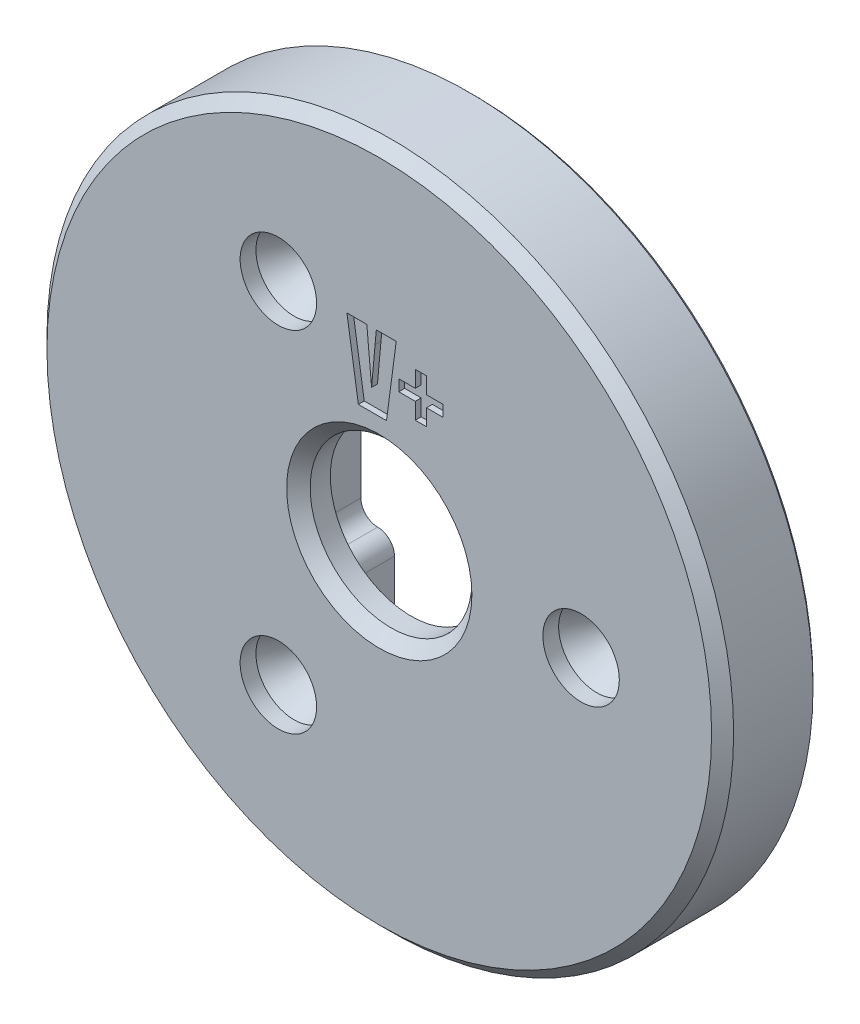
SolidWorks part; units mm, degrees
other "标注1"
sketch "草图9" plane through (123, 77, 0) normal (0.3334, -0.0407, -0.9419) x (-0.9427, 0, -0.3337)
material "有机玻璃 (TM) GS 丙烯酸铸钣"
ref_plane "前视基准面" through (0, 0, 0) normal (0, 0, 1) x (1, 0, 0)
ref_plane "上视基准面" through (0, 0, 0) normal (0, 1, 0) x (1, 0, 0)
ref_plane "右视基准面" through (0, 0, 0) normal (1, 0, 0) x (0, 0, -1)
sketch "草图2" plane through (0, 0, 0) normal (0, 0, 1) x (1, 0, 0)
  circle A2 centre (100, 100) radius 21.8
sketch "草图3" plane through (0, 0, 0) normal (0, 0, 1) x (1, 0, 0)
  circle A0 centre (100, 100) radius 23.35
extrude "凸台-拉伸3" add sketch "草图3" along normal blind 6.4
extrude "切除-拉伸1" cut sketch "草图2" along normal blind 1.63
sketch "草图4" plane through (0, 0, 0) normal (0, 0, 1) x (1, 0, 0)
  line L0 (83.312, 98.171) -> (83.312, 101.854)
  line L1 (83.566, 97.917) -> (86.868, 97.917)
  line L2 (87.122, 98.171) -> (87.122, 101.727)
  line L3 (83.566, 102.108) -> (86.741, 102.108)
  line L4 (98.171, 114.173) -> (98.171, 115.57)
  line L5 (96.901, 114.173) -> (98.171, 114.173)
  line L6 (96.393, 106.045) -> (96.393, 113.665)
  line L7 (93.98, 97.155) -> (93.98, 103.632)
  line L8 (96.266, 83.693) -> (96.266, 94.869)
  line L9 (96.901, 83.058) -> (102.489, 83.058)
  line L10 (103.759, 84.328) -> (106.807, 84.328)
  line L11 (107.188, 84.709) -> (108.712, 84.709)
  line L12 (109.347, 85.344) -> (109.347, 86.868)
  line L13 (109.855, 87.376) -> (110.871, 87.376)
  line L14 (111.379, 87.884) -> (111.379, 88.646)
  line L15 (111.887, 89.154) -> (114.046, 89.154)
  line L16 (114.554, 89.662) -> (114.554, 91.059)
  line L17 (115.062, 91.567) -> (115.189, 91.567)
  line L18 (115.824, 92.202) -> (115.824, 94.615)
  line L19 (106.299, 94.869) -> (115.57, 94.869)
  line L20 (105.791, 95.377) -> (105.791, 102.616)
  line L21 (106.426, 103.251) -> (115.443, 103.251)
  line L22 (116.586, 102.108) -> (117.983, 102.108)
  line L23 (118.237, 102.362) -> (118.237, 102.997)
  line L24 (116.713, 104.521) -> (116.713, 109.093)
  line L25 (111.252, 109.855) -> (115.951, 109.855)
  line L26 (110.744, 110.363) -> (110.744, 113.411)
  line L27 (103.632, 114.427) -> (109.728, 114.427)
  line L28 (103.251, 114.808) -> (103.251, 115.57)
  line L29 (98.552, 115.951) -> (102.87, 115.951)
  arc A60 (83.566, 102.108) -> (83.312, 101.854) centre (83.566, 101.854) ccw
  arc A63 (83.312, 98.171) -> (83.566, 97.917) centre (83.566, 98.171) ccw
  arc A66 (86.868, 97.917) -> (87.122, 98.171) centre (86.868, 98.171) ccw
  arc A69 (87.122, 101.727) -> (86.741, 102.108) centre (86.741, 101.727) ccw
  arc A72 (98.552, 115.951) -> (98.171, 115.57) centre (98.552, 115.57) ccw
  arc A75 (96.901, 114.173) -> (96.393, 113.665) centre (96.901, 113.665) ccw
  arc A78 (95.25, 104.902) -> (96.393, 106.045) centre (95.25, 106.045) ccw
  arc A81 (95.25, 104.902) -> (93.98, 103.632) centre (95.25, 103.632) ccw
  arc A84 (93.98, 97.155) -> (95.123, 96.012) centre (95.123, 97.155) ccw
  arc A87 (96.266, 94.869) -> (95.123, 96.012) centre (95.123, 94.869) ccw
  arc A90 (96.266, 83.693) -> (96.901, 83.058) centre (96.901, 83.693) ccw
  arc A93 (102.489, 83.058) -> (102.87, 83.439) centre (102.489, 83.439) ccw
  arc A96 (103.759, 84.328) -> (102.87, 83.439) centre (103.759, 83.439) ccw
  arc A99 (106.807, 84.328) -> (106.934, 84.455) centre (106.807, 84.455) ccw
  arc A102 (107.188, 84.709) -> (106.934, 84.455) centre (107.188, 84.455) ccw
  arc A105 (108.712, 84.709) -> (109.347, 85.344) centre (108.712, 85.344) ccw
  arc A108 (109.855, 87.376) -> (109.347, 86.868) centre (109.855, 86.868) ccw
  arc A111 (110.871, 87.376) -> (111.379, 87.884) centre (110.871, 87.884) ccw
  arc A114 (111.887, 89.154) -> (111.379, 88.646) centre (111.887, 88.646) ccw
  arc A117 (114.046, 89.154) -> (114.554, 89.662) centre (114.046, 89.662) ccw
  arc A120 (115.062, 91.567) -> (114.554, 91.059) centre (115.062, 91.059) ccw
  arc A123 (115.189, 91.567) -> (115.824, 92.202) centre (115.189, 92.202) ccw
  arc A126 (115.824, 94.615) -> (115.57, 94.869) centre (115.57, 94.615) ccw
  arc A129 (105.791, 95.377) -> (106.299, 94.869) centre (106.299, 95.377) ccw
  arc A132 (106.426, 103.251) -> (105.791, 102.616) centre (106.426, 102.616) ccw
  arc A135 (116.078, 102.616) -> (115.443, 103.251) centre (115.443, 102.616) ccw
  arc A138 (116.078, 102.616) -> (116.586, 102.108) centre (116.586, 102.616) ccw
  arc A141 (117.983, 102.108) -> (118.237, 102.362) centre (117.983, 102.362) ccw
  arc A144 (118.237, 102.997) -> (117.729, 103.505) centre (117.729, 102.997) ccw
  arc A147 (116.713, 104.521) -> (117.729, 103.505) centre (117.729, 104.521) ccw
  arc A150 (116.713, 109.093) -> (115.951, 109.855) centre (115.951, 109.093) ccw
  arc A153 (110.744, 110.363) -> (111.252, 109.855) centre (111.252, 110.363) ccw
  arc A156 (110.744, 113.411) -> (109.728, 114.427) centre (109.728, 113.411) ccw
  arc A159 (103.251, 114.808) -> (103.632, 114.427) centre (103.632, 114.808) ccw
  arc A162 (103.251, 115.57) -> (102.87, 115.951) centre (102.87, 115.57) ccw
extrude "切除-拉伸2" cut sketch "草图4" along normal blind 2.6 from surface contours A162 L29 A72 L4 L5 A75 L6 A78 A81 L7 A84 A87 L8 A90 L9 A93 A96 L10 A99 A102 L11 A105 L12 A108 L13 region at (104.0257, 99.7178, 0) starting at face at (121.8, 100, 1.63)
sketch "草图5" plane through (0, 0, 0) normal (0, 0, 1) x (1, 0, 0)
  circle A0 centre (113.725, 100) radius 1.35
  circle A3 centre (93.1375, 88.1138) radius 1.35
  circle A6 centre (93.1375, 111.8862) radius 1.35
  circle A9 centre (100, 100) radius 5.5
extrude "切除-拉伸3" cut sketch "草图5" along normal up to surface (6.4 mm away) from surface contours A0 | A6 | A3 | A6 region at (113.725, 100, 0) region at (93.1375, 88.1138, 0) region at (93.1375, 111.8862, 0) up to face at (123.35, 100, 6.4) starting at face at (121.8, 100, 1.63)
extrude "切除-拉伸4" cut sketch "草图5<3>" along normal up to surface (6.4 mm away) from surface contours A9 region at (100, 100, 0) up to face at (115.075, 100, 6.4) starting at face at (107.6312, 98.717, 4.23)
sketch "草图5<3>" plane through (0, 0, 0) normal (0, 0, 1) x (1, 0, 0) same geometry as "草图5"
chamfer "倒角1" distance 0.75 angle 45 1 edges at (123.35, 100, 6.4)
sketch "草图6" plane through (0, 0, 0) normal (0, 0, 1) x (1, 0, 0)
  circle A0 centre (93.1375, 111.8862) radius 2.6
  circle A1 centre (93.1375, 88.1138) radius 2.6
  circle A2 centre (113.725, 100) radius 2.6
extrude "切除-拉伸5" cut sketch "草图6" against normal blind 1 from surface starting at face at (122.6, 100, 6.4)
chamfer "倒角2" distance 1.29 distance2 2.385 3 edges at (115.075, 100, 5.4) (94.4875, 88.1138, 5.4) (94.4875, 111.8862, 5.4) first distance on face at (115.075, 100, 5.4) first distance on face at (94.4875, 88.1138, 5.4) first distance on face at (94.4875, 111.8862, 5.4)
chamfer "倒角3" distance 0.25 angle 45 2 edges at (123.35, 100, 0) (121.8, 100, 0)
chamfer "倒角4" distance 0.8 1 edges at (105.5, 100, 6.4)
sketch "草图7" plane through (0, 0, 0) normal (0, 0, 1) x (1, 0, 0)
  text T0 "V+" font "Impact" height 5
extrude "切除-拉伸7" cut sketch "草图7" against normal blind 0.4 from surface starting at face at (106.3, 100, 6.4)
sketch "草图8" plane through (0, 0, 0) normal (0, 0, 1) x (1, 0, 0)
  line L0 (82.169, 102.87) -> (83.058, 102.87)
  line L1 (83.058, 102.87) -> (83.439, 102.489)
  line L2 (83.439, 98.425) -> (83.439, 102.489)
  line L3 (83.439, 98.425) -> (83.82, 98.044)
  line L4 (83.82, 98.044) -> (86.868, 98.044)
  line L5 (86.868, 98.044) -> (87.122, 98.298)
  line L6 (87.122, 98.298) -> (87.122, 101.981)
  line L7 (87.122, 101.981) -> (87.376, 102.235)
  line L8 (87.376, 102.235) -> (91.313, 102.235)
  line L9 (91.313, 102.235) -> (91.567, 102.489)
  line L10 (91.567, 102.489) -> (91.567, 107.95)
  line L11 (91.186, 108.331) -> (91.567, 107.95)
  line L12 (88.5926, 108.331) -> (91.186, 108.331)
  line L13 (87.8407, 109.0829) -> (88.5926, 108.331)
  line L14 (85.3763, 109.0829) -> (87.8407, 109.0829)
  line L15 (85.217, 108.9236) -> (85.3763, 109.0829)
  line L16 (85.217, 108.077) -> (85.217, 108.9236)
  line L17 (84.836, 107.696) -> (85.217, 108.077)
  line L18 (83.185, 107.696) -> (84.836, 107.696)
  line L19 (82.169, 106.68) -> (83.185, 107.696)
  line L20 (82.169, 102.87) -> (82.169, 106.68)
extrude "切除-拉伸8" cut sketch "草图8" along normal blind 1.5 from surface starting at face at (115.075, 100, 1.63)
